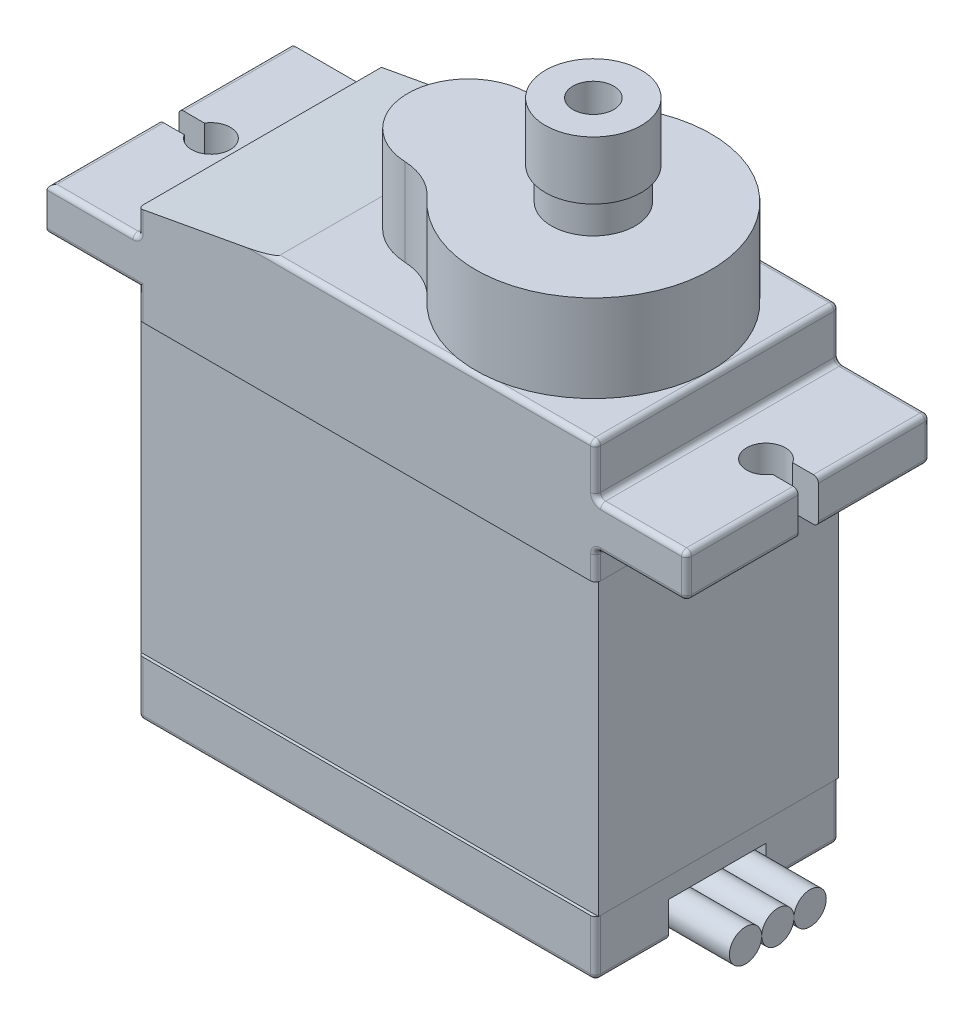
SolidWorks part; units mm, degrees
note: '?' marks a value the reader was unsure of.
ref_plane "Alzado" through (0, 0, 0) normal (0, 0, 1) x (1, 0, 0)
ref_plane "Planta" through (0, 0, 0) normal (0, 1, 0) x (1, 0, 0)
ref_plane "Vista lateral" through (0, 0, 0) normal (1, 0, 0) x (0, 0, -1)
sketch "Croquis1" plane through (0, 0, 0) normal (0, 1, 0) x (1, 0, 0)
  line L1 (-11.335, 6.03) -> (11.335, 6.03)
  line L2 (-11.335, 6.03) -> (-11.335, -6.03)
  line L3 (-11.335, -6.03) -> (11.335, -6.03)
  line L4 (11.335, 6.03) -> (11.335, -6.03)
  line L5 (-11.335, 6.03) -> (11.335, -6.03) construction
  line L6 (-11.335, -6.03) -> (11.335, 6.03) construction
  point P0 (0, 0)
  dimension "D1" = 22.67
  dimension "D2" = 12.06
extrude "Saliente-Extruir1" add sketch "Croquis1" along normal blind 23.15
sketch "Croquis2" plane through (11.335, 0, 0) normal (1, 0, 0) x (0, 0, -1)
  line L0 (-6.03, 0) -> (-6.03, 18.53) construction
  line L1 (-6.03, 23.15) -> (-6.03, 0) construction
  line L2 (-6.03, 18.53) -> (6.03, 18.53)
  line L3 (6.03, 23.15) -> (6.03, 0) construction
  line L4 (-6.03, 20.66) -> (6.03, 20.66)
  line L5 (-6.03, 20.66) -> (-6.03, 18.53)
  line L6 (6.03, 20.66) -> (6.03, 18.53)
  dimension "D1" = 18.53
  dimension "D2" = 2.13
extrude "Saliente-Extruir2" add sketch "Croquis2" along normal blind 4.51
sketch "Croquis5" plane through (-11.335, 0, 0) normal (-1, 0, 0) x (0, 0, 1)
  line L1 (6.03, 23.15) -> (6.03, 0) construction
  line L2 (-6.03, 20.66) -> (6.03, 20.66)
  line L3 (-6.03, 20.66) -> (-6.03, 18.53)
  line L4 (-6.03, 18.53) -> (6.03, 18.53)
  line L5 (6.03, 20.66) -> (6.03, 18.53)
  line L8 (-6.03, 0) -> (6.03, 0) construction
  dimension "D1" = 18.53
extrude "Saliente-Extruir3" add sketch "Croquis5" along normal blind 4.51
fillet "Redondeo1" radius 0.25 30 edges at (11.335, 0, 0) (0, 0, -6.03) (0, 0, 6.03) (-11.335, 0, 0) (0, 23.15, -6.03) (0, 23.15, 6.03) (-11.335, 23.15, 0) (11.335, 23.15, 0) (15.845, 19.595, -6.03) (15.845, 19.595, 6.03) (15.845, 18.53, 0) (15.845, 20.66, 0) (-15.845, 18.53, 0) (-15.845, 20.66, 0)
sketch "Croquis6" plane through (0, 20.66, 0) normal (0, 1, 0) x (1, 0, 0)
  line L0 (-15.595, 6.03) -> (-11.585, -5.78) construction
  line L1 (-11.585, -5.78) -> (-11.585, 6.03) construction
  line L2 (-11.585, 6.03) -> (-15.595, -5.78) construction
  line L3 (0, 0) -> (0, 5.78) construction
  line L4 (11.085, 5.78) -> (-11.085, 5.78) construction
  line L5 (0, 5.78) -> (0, -5.78) construction
  line L6 (-11.085, -5.78) -> (11.085, -5.78) construction
  line L7 (-22.4686, 0) -> (24.1195, 0) construction
  line L9 (-14.5695, 0.5) -> (-16.5695, 0.5)
  line L10 (-14.5695, -0.5) -> (-16.5695, -0.5)
  line L11 (-16.5695, -0.5) -> (-16.5695, 0.5)
  line L12 (14.5695, 0.5) -> (16.5695, 0.5)
  line L13 (16.5695, -0.5) -> (16.5695, 0.5)
  line L14 (14.5695, -0.5) -> (16.5695, -0.5)
  arc A0 (-14.5695, -0.5) -> (-14.5695, 0.5) centre (-13.75, 0) ccw
  arc A1 (14.5695, -0.5) -> (14.5695, 0.5) centre (13.75, 0) cw
  point P20 (-16.5695, 0)
  dimension "D1" = 1.92
  dimension "D2" = 27.5
  dimension "D3" = 1
  dimension "D4" = 2
extrude "Cortar-Extruir12" cut sketch "Croquis6" against normal blind 4.51
sketch "Croquis8" plane through (0, 23.15, 0) normal (0, 1, 0) x (1, 0, 0)
  line L0 (11.085, 0) -> (-11.085, 0) construction
  line L1 (0, 15.0354) -> (0, -9.7672) construction
  line L2 (13.75, 2.8581) -> (13.75, -7.7295) construction
  line L3 (11.085, -5.78) -> (11.085, 5.78) construction
  line L4 (-11.085, 5.78) -> (-11.085, -5.78) construction
  line L5 (11.085, 5.78) -> (-11.085, 5.78) construction
  line L6 (11.085, 0) -> (-1, 0) construction
  arc A0 (0.9293, -3.9766) -> (0.999, 3.9421) centre (5.25, -0.055) ccw
  arc A1 (-1.0933, 2.9985) -> (-1.146, -2.9964) centre (-1, 0) ccw
  arc A2 (-1.146, -2.9964) -> (0.9293, -3.9766) centre (-1.2921, -5.9929) cw
  arc A3 (-1.0933, 2.9985) -> (0.999, 3.9421) centre (-1.1866, 5.9971) ccw
  dimension "D1" = 3
  dimension "D3" = 1
  dimension "D4" = 3
  dimension "D2" = 8.5
extrude "Saliente-Extruir4" add sketch "Croquis8" along normal blind 4.32 separate body
sketch "Croquis9" plane through (0, 27.47, 0) normal (0, 1, 0) x (1, 0, 0)
  line L0 (5.25, 5.78) -> (5.25, -0.055) construction
  line L1 (11.085, 5.78) -> (-11.085, 5.78) construction
  arc A0 (0.9293, -3.9766) -> (0.999, 3.9421) centre (5.25, -0.055) ccw construction
  circle A1 centre (5.25, -0.055) radius 2.075
  dimension "D1" = 4.15
extrude "Saliente-Extruir5" add sketch "Croquis9" along normal blind 1.58 separate body
sketch "Croquis10" plane through (0, 29.05, 0) normal (0, 1, 0) x (1, 0, 0)
  circle A0 centre (5.25, -0.055) radius 2.385
extrude "Saliente-Extruir6" add sketch "Croquis10" along normal blind 2.88 separate body
sketch "Croquis11" plane through (0, 31.93, 0) normal (0, 1, 0) x (1, 0, 0)
  circle A0 centre (5.25, -0.055) radius 1.01
  dimension "D1" = 2.02
extrude "Cortar-Extruir13" cut sketch "Croquis11" against normal blind 3.88
sketch "Croquis12" plane through (0, 31.93, 0) normal (0, 1, 0) x (1, 0, 0)
  circle A2 centre (5.25, -0.055) radius 2.375
  circle A3 centre (5.25, -0.055) radius 2.385
  dimension "D4" = 4.75
extrude "Cortar-Extruir14" cut sketch "Croquis12" along a picked direction on the side against the normal blind 2.88
sketch "Croquis13" plane through (0, 0, 6.03) normal (0, 0, 1) x (1, 0, 0)
  line L0 (-4.5405, 23.15) -> (-11.335, 21.905) construction
  line L1 (-11.085, 23.15) -> (11.085, 23.15) construction
  line L2 (-11.335, 20.91) -> (-11.335, 22.9) construction
  line L3 (-4.5405, 23.15) -> (-11.335, 21.905)
  line L4 (-11.335, 21.905) -> (-11.335, 23.15)
  line L5 (-11.335, 23.15) -> (-4.5405, 23.15)
extrude "Cortar-Extruir15" cut sketch "Croquis13" against normal blind 16.88
sketch "Croquis14" plane through (0, 0, 6.03) normal (0, 0, 1) x (1, 0, 0)
  line L0 (-11.085, 15.1) -> (11.085, 15.1)
  line L1 (-11.085, 18.78) -> (-11.085, 0.25) construction
  line L2 (11.085, 0.25) -> (11.085, 18.28) construction
  line L3 (11.085, 22.9) -> (-5.9049, 22.9) construction
  line L4 (-11.085, 2.77) -> (11.085, 2.77)
  line L5 (-11.085, 0.25) -> (11.085, 0.25) construction
  line L6 (11.085, 15.1) -> (11.085, 2.77)
  line L7 (-11.085, 15.1) -> (-11.085, 2.77)
  dimension "D1" = 7.8
  dimension "D2" = 2.52
extrude "Cortar-Extruir16" cut sketch "Croquis14" against normal blind 16.88
sketch "Croquis16" plane through (-11.335, 0, 0) normal (-1, 0, 0) x (0, 0, 1)
  line L0 (5.78, 17.1096) -> (-5.78, 17.1096)
  line L3 (5.78, 0.25) -> (5.78, 18.53) construction
  line L4 (-5.78, 18.53) -> (-5.78, 0.25) construction
  line L5 (-5.78, 2.7548) -> (5.78, 2.7548)
  line L6 (5.78, 17.1096) -> (5.78, 2.7548)
  line L7 (-5.78, 2.7548) -> (-5.78, 17.1096)
extrude "Cortar-Extruir17" cut sketch "Croquis16" against normal blind 27.88
sketch "Croquis17" plane through (0, 0, 0) normal (0, 0, 1) x (1, 0, 0)
  line L0 (-11.335, 17.1096) -> (11.335, 17.1096)
  line L1 (11.335, 17.1096) -> (11.335, 2.7548)
  line L2 (11.335, 2.7548) -> (-11.335, 2.7548)
  line L3 (-11.335, 2.7548) -> (-11.335, 17.1096)
extrude "Cortar-Extruir18" cut sketch "Croquis17" against normal blind 27.88 and the other way blind 27.88
sketch "Croquis18" plane through (0, 0, 0) normal (0, 0, 1) x (1, 0, 0)
  line L0 (-11.335, 17.1096) -> (-11.335, 2.7548)
  line L1 (-11.335, 2.7548) -> (11.335, 2.7548)
  line L2 (11.335, 2.7548) -> (11.335, 17.1096)
  line L3 (11.335, 17.1096) -> (-11.335, 17.1096)
extrude "Saliente-Extruir7" add sketch "Croquis18" along normal blind 5.88 and the other way blind 6 separate body
sketch "Croquis19" plane through (11.335, 0, 0) normal (1, 0, 0) x (0, 0, -1)
  line L0 (5.78, 1.5024) -> (2.42, 1.5024) construction
  line L1 (5.78, 0.25) -> (5.78, 2.7548) construction
  line L2 (0, 2.7548) -> (0, 1.7548) construction
  line L4 (-5.78, 1.5024) -> (-2.42, 1.5024) construction
  line L5 (6, 2.7548) -> (-5.88, 2.7548) construction
  line L6 (-2.42, 1.7548) -> (2.42, 1.7548)
  line L7 (2.42, 1.7548) -> (2.42, 0)
  line L8 (5.78, 0) -> (-5.78, 0) construction
  line L9 (2.42, 0) -> (-2.42, 0)
  line L10 (-2.42, 0) -> (-2.42, 1.7548)
  dimension "D1" = 3.36
  dimension "D2" = 1
extrude "Cortar-Extruir19" cut sketch "Croquis19" against normal blind 1.6
sketch "Croquis20" plane through (9.735, 0, 0) normal (1, 0, 0) x (0, 0, -1)
  line L0 (0, 1.7548) -> (0, 0) construction
  line L1 (2.42, 1.7548) -> (-2.42, 1.7548) construction
  line L2 (0, 0.8774) -> (2.42, 0.8774) construction
  line L3 (2.42, 0) -> (2.42, 1.7548) construction
  line L4 (0, 0.8774) -> (-2.42, 0.8774) construction
  line L5 (-2.42, 1.7548) -> (-2.42, 0) construction
  circle A0 centre (0, 0.8774) radius 0.8
  circle A1 centre (-1.6, 0.8774) radius 0.8
  circle A2 centre (1.6, 0.8774) radius 0.8
  dimension "D1" = 1.6
  dimension "D2" = 1.6
  dimension "D3" = 1.6
extrude "Saliente-Extruir8" add sketch "Croquis20" along normal blind 4.6 separate body contours A1 | A0 | A2
ref_axis "Axis1" through (5.25, 29.05, 0.055) along (0, 1, 0)?
ref_plane "Plane1" through (5.25, 0, 0) normal (1, 0, 0) x (0, 0, -1)
ref_plane "Plane2" through (5.25, 0, 0) normal (1, 0, 0) x (0, 0, -1)
ref_axis "Axis2" through (5.25, 29.05, 0.055) along (0, 1, 0)?
